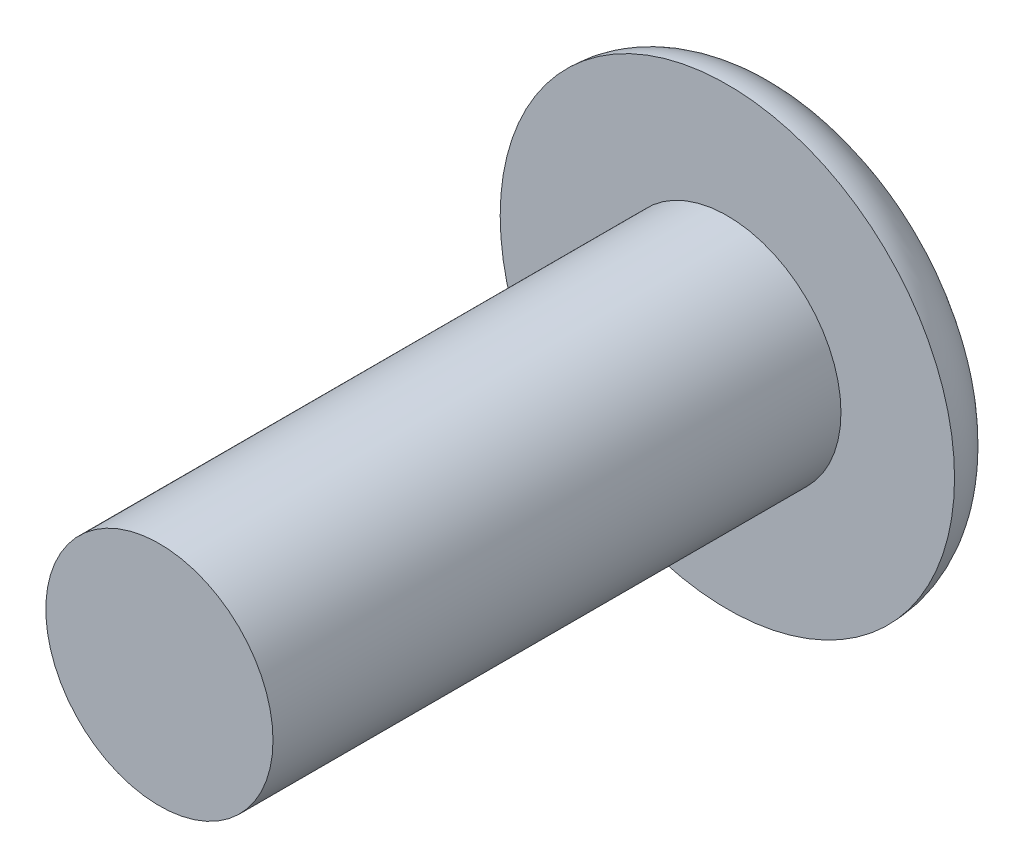
SolidWorks part; units mm, degrees
ref_plane "Front Plane" through (0, 0, 0) normal (0, 0, 1) x (1, 0, 0)
ref_plane "Top Plane" through (0, 0, 0) normal (0, 1, 0) x (1, 0, 0)
ref_plane "Right Plane" through (0, 0, 0) normal (1, 0, 0) x (0, 0, -1)
sketch "Sketch1" plane through (0, 0, 0) normal (0, 0, 1) x (1, 0, 0)
  circle A0 centre (0, 0) radius 4
  dimension "D1" = 8
extrude "Boss-Extrude1" add sketch "Sketch1" along normal blind 1
sketch "Sketch2" plane through (0, 0, 1) normal (0, 0, 1) x (1, 0, 0)
  circle A0 centre (0, 0) radius 2
  dimension "D1" = 4
extrude "Boss-Extrude2" add sketch "Sketch2" along normal blind 10
fillet "Fillet2" radius 1 1 edges at (4, 0, 0)
equation "\"pin_head_d\" = 8"
equation "\"D1@Sketch1\"=\"pin_head_d\""
equation "\"head_t\"= 1"
equation "\"D1@Boss-Extrude1\"=\"head_t\""
equation "\"pin_length\"=10"
equation "\"D1@Boss-Extrude2\"=\"pin_length\""
equation "\"fillet_size\"=1"
equation "\"D1@Fillet2\"=\"fillet_size\""
equation "\"pin_d\"=4"
equation "\"D1@Sketch2\"=\"pin_d\""
